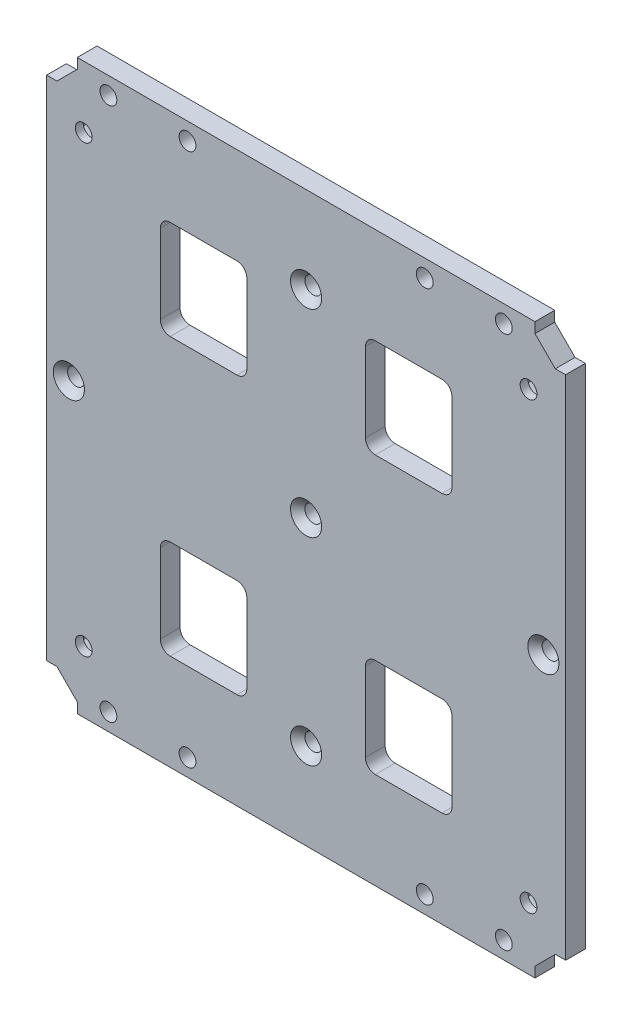
SolidWorks part; units mm, degrees
ref_plane "1" through (0, 0, 0) normal (0, 0, 1) x (1, 0, 0)
ref_plane "2" through (0, 0, 0) normal (0, 1, 0) x (1, 0, 0)
ref_plane "3" through (0, 0, 0) normal (1, 0, 0) x (0, 0, -1)
ref_plane "Front Plane" through (0, 0, 0) normal (0, -1, 0) x (1, 0, 0)
ref_plane "Right Plane" through (0, 0, 0) normal (1, 0, 0) x (0, 1, 0)
ref_plane "Top Plane" through (0, 0, 0) normal (0, 0, 1) x (1, 0, 0)
ref_plane "Plane1" through (0, 0, 1.6) normal (0, 0, 1) x (1, 0, 0)
sketch "Sketch1" plane through (0, 0, 0) normal (0, 0, 1) x (1, 0, 0)
  line L0 (-52.5, 57.5) -> (52.5, 57.5) construction
  line L1 (-52.5, 57.5) -> (-52.5, -57.5) construction
  line L2 (52.5, 57.5) -> (52.5, -57.5) construction
  line L3 (-52.5, -57.5) -> (52.5, -57.5) construction
  line L4 (0, 57.5) -> (0, 66.5129) construction
  line L5 (52.5, 0) -> (80.0122, 0) construction
  line L14 (-45, 45) -> (45, 45) construction
  line L15 (-45, 45) -> (-45, -45) construction
  line L16 (45, 45) -> (45, -45) construction
  line L17 (-45, -45) -> (45, -45) construction
  line L18 (0, 45) -> (0, 40.4761) construction
  line L19 (45, 0) -> (34.1739, 0) construction
  circle A0 centre (45, 45) radius 1.5 construction
  circle A1 centre (-45, 45) radius 1.5 construction
  circle A2 centre (-45, -45) radius 1.5 construction
  circle A3 centre (45, -45) radius 1.5 construction
  dimension "D4" = 3
  dimension "D1" = 105
  dimension "D2" = 115
  dimension "D3" = 90
  dimension "D5" = 90
sketch "Sketch2" plane through (0, 0, 0) normal (0, 0, 1) x (1, 0, 0)
  line L8 (0, 57.5) -> (0, 0)
  line L9 (0, 0) -> (52.5, 0)
  line L10 (52.5, 0) -> (52.5, 51.5)
  line L11 (52.5, 51.5) -> (50.5, 51.5)
  line L12 (50.5, 51.5) -> (46.5, 55.5)
  line L13 (46.5, 55.5) -> (46.5, 57.5)
  line L14 (46.5, 57.5) -> (0, 57.5)
  line L15 (-52.5, 57.5) -> (52.5, 57.5) construction
  line L16 (52.5, 57.5) -> (52.5, -57.5) construction
  line L19 (46.5, 55.5) -> (44.5, 57.5) construction
  dimension "D1" = 45
  dimension "D2" = 8
  dimension "D3" = 6
extrude "Boss-Extrude1" add sketch "Sketch2" along normal blind 4
sketch "Sketch12" plane through (0, 0, 0) normal (0, 0, 1) x (1, 0, 0)
  line L1 (45, 41.7668) -> (47.8, 43.3834)
  line L2 (47.8, 43.3834) -> (47.8, 46.6166)
  line L3 (47.8, 46.6166) -> (45, 48.2332)
  line L4 (45, 48.2332) -> (42.2, 46.6166)
  line L5 (42.2, 46.6166) -> (42.2, 43.3834)
  line L6 (42.2, 43.3834) -> (45, 41.7668)
  circle A0 centre (45, 45) radius 2.8 construction
  circle A1 centre (45, 45) radius 1.5 construction
  dimension "D1" = 5.6
extrude "Cut-Extrude4" cut sketch "Sketch12" along normal blind 2.4
hole_wizard "M3 Clearance Hole1" positions "Sketch3" profile "Sketch5" hole size "M3" standard "ANSI Metric" end condition through all
sketch "Sketch3" plane through (0, 0, 4) normal (0, 0, 1) x (1, 0, 0)
  circle A0 centre (45, 45) radius 1.5 construction
  circle A1 centre (-45, 45) radius 1.5 construction
  circle A2 centre (-45, -45) radius 1.5 construction
  circle A3 centre (45, -45) radius 1.5 construction
  point P0 (45, 45)
  point P2 (-45, 45)
  point P4 (-45, -45)
  point P6 (45, -45)
sketch "Sketch5" plane through (45, 45, 4) normal (1, 0, 0) x (0, -1, 0)
  line L0 (0, 0) -> (0, 4)
  line L1 (0, 4) -> (1.7, 4)
  line L2 (1.7, 4) -> (1.7, 0)
  line L5 (1.7, 0) -> (0, 0)
  line L11 (0, -6.35) -> (0, 107.95) construction
  dimension "Thru Hole Dia." = 3.4
  dimension "Thru Hole Depth" = 4
sketch "Sketch6" plane through (0, 0, 0) normal (0, 0, 1) x (1, 0, 0)
  line L0 (0, 40) -> (0, 0) construction
  line L1 (0, 0) -> (48, 0) construction
  circle A3 centre (0, 40) radius 1.5
  circle A4 centre (0, 0) radius 1.5
  circle A5 centre (48, 0) radius 1.5
  dimension "D1" = 3
  dimension "D2" = 40
  dimension "D3" = 48
hole_wizard "CSK for M3 Flat Head Machine Screw1" positions "Sketch9" profile "Sketch10" countersink size "M3" standard "ANSI Metric" end condition through all
sketch "Sketch9" plane through (0, 0, 4) normal (0, 0, 1) x (1, 0, 0)
  circle A3 centre (0, 40) radius 1.5 construction
  circle A4 centre (0, 0) radius 1.5 construction
  circle A5 centre (48, 0) radius 1.5 construction
  point P0 (0, 40)
  point P2 (0, 0)
  point P4 (48, 0)
  point P11 (0, 0)
  point P14 (9.8413, 34.146)
  point P17 (-13.8923, 3.0323)
  point P20 (60.4953, 2.9485)
sketch "Sketch10" plane through (0, 40, 4) normal (1, 0, 0) x (0, -1, 0)
  line L0 (0, 0) -> (0, 4)
  line L1 (0, 4) -> (1.7, 4)
  line L2 (1.7, 4) -> (1.7, 1.45)
  line L3 (1.7, 1.45) -> (3.15, 0)
  line L5 (3.15, 0) -> (0, 0)
  line L6 (-1.7, 1.45) -> (-3.15, 0) construction
  line L11 (0, -6.35) -> (0, 107.95) construction
  dimension "Thru Hole Dia." = 3.4
  dimension "Thru Hole Depth" = 4
  dimension "Near C'Sink Dia." = 6.3
  dimension "Near C'Sink Angle" = 90
sketch "Sketch11" plane through (0, 0, 0) normal (0, 0, 1) x (1, 0, 0)
  line L0 (12, 38) -> (12, 18)
  line L1 (12, 38) -> (29.5, 38)
  line L2 (12, 18) -> (29.5, 18)
  line L3 (29.5, 38) -> (29.5, 18)
  line L4 (12, 28) -> (8.7244, 28) construction
  line L5 (0, -31.3359) -> (0, 31.3359) construction
  dimension "D1" = 28
  dimension "D2" = 20
  dimension "D3" = 12
  dimension "D4" = 29.5
extrude "Cut-Extrude3" cut sketch "Sketch11" along normal through all
fillet "Fillet1" radius 2 4 edges at (12, 18, 2) (29.5, 18, 2) (29.5, 38, 2) (12, 38, 2)
sketch "Sketch15" plane through (0, 0, 0) normal (0, 0, 1) x (1, 0, 0)
  line L0 (0, 54) -> (40, 54) construction
  line L1 (40, 54) -> (48, 54) construction
  line L2 (48, 54) -> (48, 46) construction
  line L3 (48, 46) -> (48, 0) construction
  line L4 (48, 0) -> (0, 0) construction
  line L5 (0, 0) -> (0, 54) construction
  circle A0 centre (40, 54) radius 1.5 construction
  circle A2 centre (24, 54) radius 1.5 construction
  dimension "D4" = 3
  dimension "D5" = 16
  dimension "D1" = 54
  dimension "D2" = 48
  dimension "D3" = 40
hole_wizard "CSK for M3 Flat Head Machine Screw2" positions "Sketch13" profile "Sketch14" countersink size "M3" standard "ANSI Metric" end condition through all
sketch "Sketch13" plane through (0, 0, 0) normal (0, 0, -1) x (-1, 0, 0)
  circle A0 centre (-24, 54) radius 1.5 construction
  circle A1 centre (-40, 54) radius 1.5 construction
  point P0 (-24, 54)
  point P2 (-40, 54)
  point P7 (0, 0)
  point P10 (0, 0)
  point P13 (0, 0)
sketch "Sketch14" plane through (24, 54, 0) normal (1, 0, 0) x (0, 1, 0)
  line L0 (0, 0) -> (0, 4)
  line L1 (0, 4) -> (1.7, 4)
  line L2 (1.7, 4) -> (1.7, 1.45)
  line L3 (1.7, 1.45) -> (3.15, 0)
  line L5 (3.15, 0) -> (0, 0)
  line L6 (-1.7, 1.45) -> (-3.15, 0) construction
  line L11 (0, -6.35) -> (0, 107.95) construction
  dimension "Thru Hole Dia." = 3.4
  dimension "Thru Hole Depth" = 4
  dimension "Near C'Sink Dia." = 6.3
  dimension "Near C'Sink Angle" = 90
other "Move Face1" flip direction yes face at (46.5, 56.5, 2) face at (48.5, 53.5, 2) face at (51.5, 51.5, 2) offset 0.2 parameters "D1"=0.2
mirror "Mirror1" about plane through (0, 0, 0) normal (0, -1, 0) of bodies 105 102
mirror "Mirror2" about plane through (0, 0, 0) normal (1, 0, 0) of bodies 103
